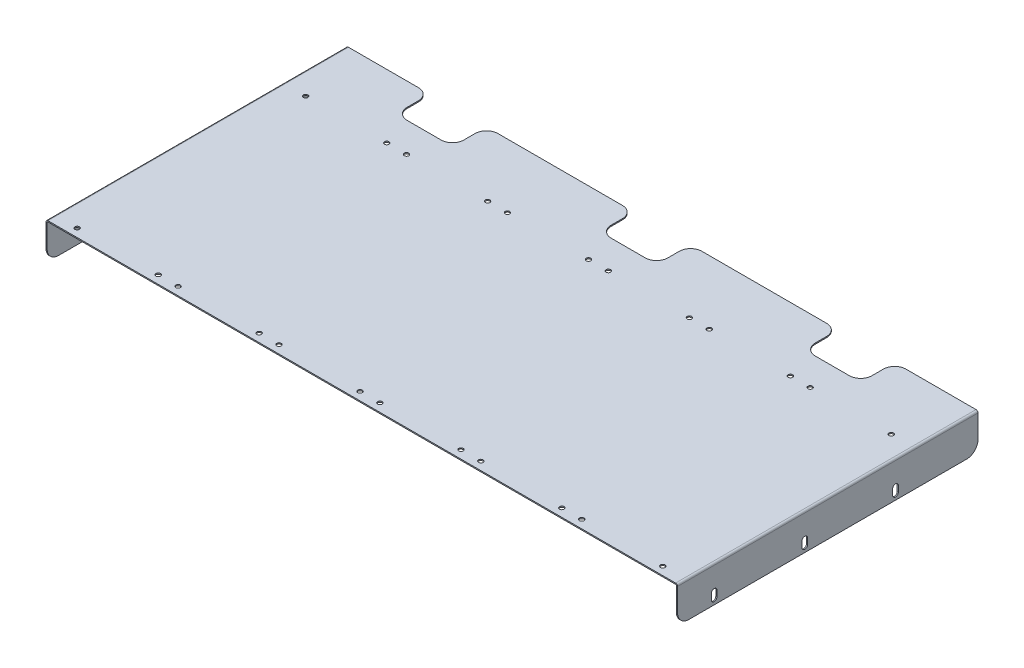
SolidWorks part; units mm, degrees
note: The reader was unsure of these and kept them because the rebuilt part matched: flange length of "Odgięcie krawędzi1".
ref_plane "Płaszczyzna przednia" through (0, 0, 0) normal (0, 0, 1) x (1, 0, 0)
ref_plane "Płaszczyzna górna" through (0, 0, 0) normal (0, 1, 0) x (1, 0, 0)
ref_plane "Płaszczyzna prawa" through (0, 0, 0) normal (1, 0, 0) x (0, 0, -1)
sketch "Szkic2" plane through (0, 0, 0) normal (0, 1, 0) x (1, 0, 0)
  line L1 (-277.5, -132.5) -> (277.5, -132.5)
  line L2 (-277.5, -132.5) -> (-277.5, 132.5)
  line L3 (-277.5, 132.5) -> (277.5, 132.5)
  line L4 (277.5, -132.5) -> (277.5, 132.5)
  line L5 (-277.5, -132.5) -> (277.5, 132.5) construction
  line L6 (-277.5, 132.5) -> (277.5, -132.5) construction
  point P0 (0, 0)
  dimension "D1" = 555
  dimension "D2" = 265
base flange "Odgięcie bazowe1" sketch "Szkic2" thickness 1 reverse thickness direction no parameters "D1"=0.7366
edge flange "Odgięcie krawędzi1" sketch "Szkic11" flange profiles "Szkic11", "Szkic12" flange angle 90 flange length 32 flange position material outside bend radius 0.7366 thickness 1 relief rectangular parameters "D6"=10, "D8"=1
sketch "Szkic11" plane through (-277.5, -1, 0) normal (-1, 0, 0) x (0, 0, -1)
  line L0 (132.5, 0) -> (-132.5, 0) construction
  line L1 (132.5, 0) -> (-132.5, 0)
  line L2 (-132.5, 0) -> (-132.5, 31)
  line L3 (-132.5, 31) -> (132.5, 31)
  line L4 (132.5, 31) -> (132.5, 0)
sketch "Szkic12" plane through (277.5, -1, 0) normal (1, 0, 0) x (0, 0, 1)
  line L0 (132.5, 0) -> (-132.5, 0) construction
  line L1 (132.5, 0) -> (-132.5, 0)
  line L2 (-132.5, 0) -> (-132.5, 31)
  line L3 (-132.5, 31) -> (132.5, 31)
  line L4 (132.5, 31) -> (132.5, 0)
bend "Zgięcie krawędziowe1" bend radius 0.7366 bend angle 90 parameters "D5"=1
bend "Zgięcie krawędziowe2" bend radius 0.7366 bend angle 90 parameters "D5"=2
sketch "Szkic15" plane through (278.5, 0, 0) normal (1, 0, 0) x (0, 0, -1)
  line L0 (-100.25, -22) -> (-100.25, -27) construction
  line L1 (-97.75, -22) -> (-97.75, -27)
  line L2 (-102.75, -22) -> (-102.75, -27)
  line L3 (-132.5, -1.7366) -> (-132.5, -32) construction
  line L4 (-132.5, -32) -> (132.5, -32) construction
  line L6 (-22.75, -22) -> (-22.75, -27)
  line L7 (-17.75, -22) -> (-17.75, -27)
  line L8 (-20.25, -22) -> (-20.25, -27) construction
  line L9 (57.25, -22) -> (57.25, -27)
  line L10 (62.25, -22) -> (62.25, -27)
  line L11 (59.75, -22) -> (59.75, -27) construction
  arc A0 (-97.75, -22) -> (-102.75, -22) centre (-100.25, -22) ccw
  arc A1 (-102.75, -27) -> (-97.75, -27) centre (-100.25, -27) ccw
  arc A2 (-17.75, -22) -> (-22.75, -22) centre (-20.25, -22) ccw
  arc A3 (-22.75, -27) -> (-17.75, -27) centre (-20.25, -27) ccw
  arc A4 (62.25, -22) -> (57.25, -22) centre (59.75, -22) ccw
  arc A5 (57.25, -27) -> (62.25, -27) centre (59.75, -27) ccw
  point P2 (-100.25, -24.5)
  point P15 (-20.25, -24.5)
  point P22 (59.75, -24.5)
  dimension "D1" = 5
  dimension "D2" = 32.25
  dimension "D3" = 5
  dimension "D4" = 5
  dimension "D5" = 3
extrude "Wytnij-wyciągnięcie3" cut sketch "Szkic15" against normal through all normal cut yes
fillet "Zaokrąglenie2" radius 10 4 edges at (-278, -32, 132.5) (-278, -32, -132.5) (278, -32, -132.5) (278, -32, 132.5)
sketch "Szkic16" plane through (0, 0, 0) normal (0, 1, 0) x (1, 0, 0)
  line L0 (0, 132.5) -> (0, -132.5) construction
  line L1 (276.7634, 132.5) -> (-276.7634, 132.5) construction
  line L2 (-276.7634, -132.5) -> (276.7634, -132.5) construction
  line L3 (-278.5, 132.5) -> (-278.5, -132.5) construction
  circle A0 centre (-258.25, -125.25) radius 2
  circle A1 centre (-186.75, -125.25) radius 2
  circle A2 centre (-258.25, 76.25) radius 2
  circle A3 centre (-186.75, 76.25) radius 2
  circle A4 centre (-169.25, 76.25) radius 2
  circle A5 centre (-97.75, 76.25) radius 2
  circle A6 centre (-169.25, -125.25) radius 2
  circle A7 centre (-97.75, -125.25) radius 2
  circle A8 centre (-80.25, 76.25) radius 2
  circle A9 centre (-8.75, 76.25) radius 2
  circle A10 centre (-80.25, -125.25) radius 2
  circle A11 centre (-8.75, -125.25) radius 2
  circle A12 centre (8.75, 76.25) radius 2
  circle A13 centre (80.25, 76.25) radius 2
  circle A14 centre (8.75, -125.25) radius 2
  circle A15 centre (80.25, -125.25) radius 2
  circle A16 centre (97.75, 76.25) radius 2
  circle A17 centre (169.25, 76.25) radius 2
  circle A18 centre (97.75, -125.25) radius 2
  circle A19 centre (169.25, -125.25) radius 2
  circle A20 centre (186.75, 76.25) radius 2
  circle A21 centre (258.25, 76.25) radius 2
  circle A22 centre (186.75, -125.25) radius 2
  circle A23 centre (258.25, -125.25) radius 2
  dimension "D1" = 71.5
  dimension "D3" = 4
  dimension "D5" = 201.5
  dimension "D2" = 20.25
  dimension "D4" = 7.25
  dimension "D6" = 6
extrude "Wytnij-wyciągnięcie4" cut sketch "Szkic16" against normal blind 10 normal cut yes
sketch "Szkic17" plane through (0, 0, 0) normal (0, 1, 0) x (1, 0, 0)
  line L0 (0, -132.5) -> (0, 132.5) construction
  line L1 (-276.7634, -132.5) -> (276.7634, -132.5) construction
  line L2 (276.7634, 132.5) -> (-276.7634, 132.5) construction
  line L3 (15, 102.5) -> (-15, 102.5)
  line L4 (-25, 112.5) -> (-25, 132.5)
  line L5 (25, 112.5) -> (25, 132.5)
  line L6 (-25, 132.5) -> (25, 132.5)
  line L7 (155, 132.5) -> (205, 132.5)
  line L8 (205, 112.5) -> (205, 132.5)
  line L9 (195, 102.5) -> (165, 102.5)
  line L10 (155, 112.5) -> (155, 132.5)
  line L11 (-155, 112.5) -> (-155, 132.5)
  line L12 (-195, 102.5) -> (-165, 102.5)
  line L13 (-205, 112.5) -> (-205, 132.5)
  line L14 (-155, 132.5) -> (-205, 132.5)
  arc A0 (25, 112.5) -> (15, 102.5) centre (15, 112.5) cw
  arc A1 (-25, 112.5) -> (-15, 102.5) centre (-15, 112.5) ccw
  arc A3 (205, 112.5) -> (195, 102.5) centre (195, 112.5) cw
  arc A4 (155, 112.5) -> (165, 102.5) centre (165, 112.5) ccw
  arc A5 (-155, 112.5) -> (-165, 102.5) centre (-165, 112.5) cw
  arc A6 (-205, 112.5) -> (-195, 102.5) centre (-195, 112.5) ccw
  point P9 (0, 102.5)
  dimension "D3" = 10
  dimension "D1" = 50
  dimension "D2" = 30
  dimension "D4" = 2
extrude "Wytnij-wyciągnięcie5" cut sketch "Szkic17" against normal blind 10 normal cut yes
fillet "Zaokrąglenie3" radius 10 6 edges at (205, -0.5, -132.5) (155, -0.5, -132.5) (25, -0.5, -132.5) (-25, -0.5, -132.5) (-155, -0.5, -132.5) (-205, -0.5, -132.5)
sketch "Linie zgięcia1" [suppressed] plane through (0, 0, 0) normal (0, 1, 0) x (1, 0, 0)
sketch "Ramka-graniczna1" [suppressed] plane through (0, 0, 0) normal (0, 1, 0) x (1, 0, 0)
sheet metal parameters "Arkusz blachy1" thickness 1 parameters "D1"=0.7366
flat pattern "Rozłożony model1" [suppressed]
sketch "Linie zgięcia2" plane through (0, 0, 0) normal (0, 1, 0) x (1, 0, 0)
sketch3d "Ramka-graniczna2" [suppressed]
  line L0 (-277.5, 132.5, 0) -> (277.5, 132.5, 0) construction
  line L1 (-277.5, -132.5, 0) -> (277.5, -132.5, 0) construction
  line L2 (-277.5, 132.5, 0) -> (-277.5, -132.5, 0) construction
  line L3 (277.5, 132.5, 0) -> (277.5, -132.5, 0) construction
sheet metal parameters "Arkusz blachy2" thickness 1 parameters "D1"=0.7366
flat pattern "Rozłożony model1"
sketch "Linie zgięcia2" plane through (0, 0, 0) normal (0, 1, 0) x (1, 0, 0)
  line L0 (277.7346, -132.5) -> (277.7346, 132.5) construction
  line L1 (-277.7346, 132.5) -> (-277.7346, -132.5) construction
  line L2 (277.7346, -132.5) -> (277.7346, 132.5) construction
  line L3 (-277.7346, 132.5) -> (-277.7346, -132.5) construction
sketch3d "Ramka-graniczna2" [suppressed]
  line L0 (308.9692, 132.5, 0) -> (-308.9692, 132.5, 0) construction
  line L1 (308.9692, -132.5, 0) -> (-308.9692, -132.5, 0) construction
  line L2 (308.9692, 132.5, 0) -> (308.9692, -132.5, 0) construction
  line L3 (-308.9692, 132.5, 0) -> (-308.9692, -132.5, 0) construction
bend of the flat pattern "Rozłożone-<Zgięcie krawędziowe1>1"
bend of the flat pattern "Rozłożone-<Zgięcie krawędziowe2>1"
sheet metal parameters "Arkusz blachy5" thickness 1 parameters "D1"=0.7366
flat pattern "Rozłożony model1"
sketch "Linie zgięcia2" plane through (0, 0, 0) normal (0, 1, 0) x (1, 0, 0)
  line L0 (277.7346, -132.5) -> (277.7346, 132.5) construction
  line L1 (-277.7346, 132.5) -> (-277.7346, -132.5) construction
  line L2 (277.7346, -132.5) -> (277.7346, 132.5) construction
  line L3 (-277.7346, 132.5) -> (-277.7346, -132.5) construction
sketch3d "Ramka-graniczna2" [suppressed]
  line L0 (-308.9692, 132.5, 0) -> (308.9692, 132.5, 0) construction
  line L1 (-308.9692, -132.5, 0) -> (308.9693, -132.5, 0) construction
  line L2 (-308.9692, 132.5, 0) -> (-308.9692, -132.5, 0) construction
  line L3 (308.9692, 132.5, 0) -> (308.9693, -132.5, 0) construction
bend of the flat pattern "Rozłożone-<Zgięcie krawędziowe1>1"
bend of the flat pattern "Rozłożone-<Zgięcie krawędziowe2>1"
sheet metal parameters "Arkusz blachy6" thickness 1 parameters "D1"=0.7366
flat pattern "Rozłożony model1"
sketch "Linie zgięcia2" plane through (0, 0, 0) normal (0, 1, 0) x (1, 0, 0)
  line L0 (277.7346, -132.5) -> (277.7346, 132.5) construction
  line L1 (-277.7346, 132.5) -> (-277.7346, -132.5) construction
  line L2 (277.7346, -132.5) -> (277.7346, 132.5) construction
  line L3 (-277.7346, 132.5) -> (-277.7346, -132.5) construction
sketch3d "Ramka-graniczna2" [suppressed]
  line L0 (-308.9692, 132.5, 0) -> (308.9692, 132.5, 0) construction
  line L1 (-308.9692, -132.5, 0) -> (308.9693, -132.5, 0) construction
  line L2 (-308.9692, 132.5, 0) -> (-308.9692, -132.5, 0) construction
  line L3 (308.9692, 132.5, 0) -> (308.9693, -132.5, 0) construction
bend of the flat pattern "Rozłożone-<Zgięcie krawędziowe1>1"
bend of the flat pattern "Rozłożone-<Zgięcie krawędziowe2>1"
sheet metal parameters "Arkusz blachy7" thickness 1 parameters "D1"=0.7366
flat pattern "Rozłożony model1"
sketch "Linie zgięcia2" plane through (0, 0, 0) normal (0, 1, 0) x (1, 0, 0)
  line L0 (277.7346, -132.5) -> (277.7346, 132.5) construction
  line L1 (-277.7346, 132.5) -> (-277.7346, -132.5) construction
  line L2 (277.7346, -132.5) -> (277.7346, 132.5) construction
  line L3 (-277.7346, 132.5) -> (-277.7346, -132.5) construction
sketch3d "Ramka-graniczna2" [suppressed]
  line L0 (-308.9692, 132.5, 0) -> (308.9692, 132.5, 0) construction
  line L1 (-308.9692, -132.5, 0) -> (308.9693, -132.5, 0) construction
  line L2 (-308.9692, 132.5, 0) -> (-308.9692, -132.5, 0) construction
  line L3 (308.9692, 132.5, 0) -> (308.9693, -132.5, 0) construction
bend of the flat pattern "Rozłożone-<Zgięcie krawędziowe1>1"
bend of the flat pattern "Rozłożone-<Zgięcie krawędziowe2>1"
